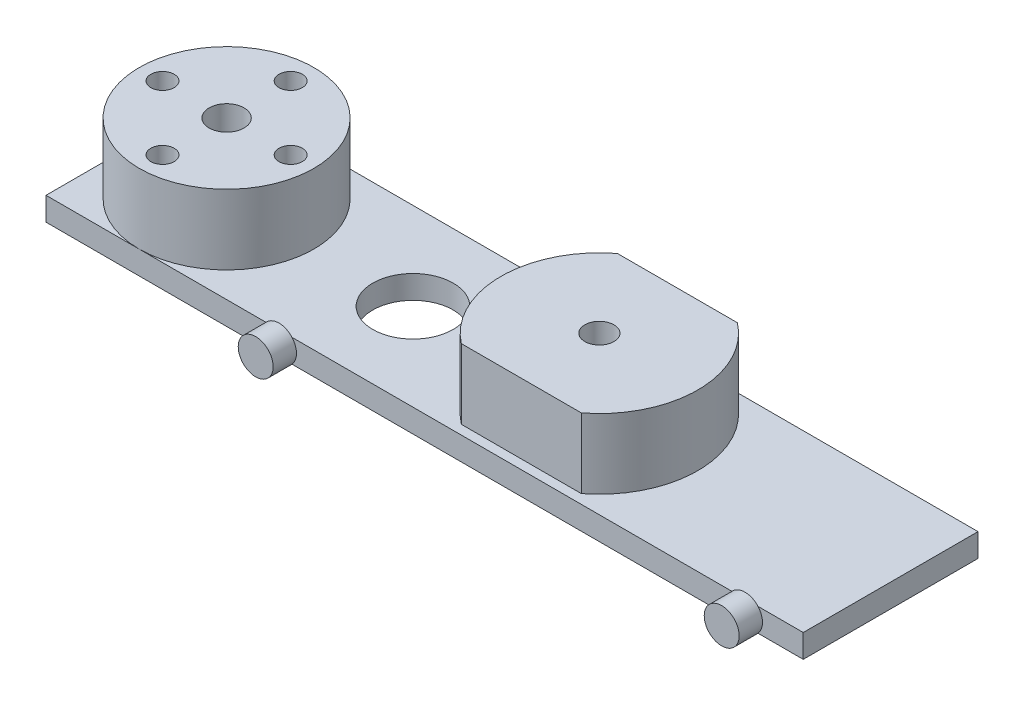
SolidWorks part; units mm, degrees
ref_plane "前视基准面" through (0, 0, 0) normal (0, 0, 1) x (1, 0, 0)
ref_plane "上视基准面" through (0, 0, 0) normal (0, 1, 0) x (1, 0, 0)
ref_plane "右视基准面" through (0, 0, 0) normal (1, 0, 0) x (0, 0, -1)
other "Configuration Table"
sketch "草图1" plane through (0, 0, 0) normal (0, 1, 0) x (1, 0, 0)
  line L0 (0, 7.5) -> (0, -7.5) construction
  line L1 (-25, 7.5) -> (25, 7.5)
  line L2 (-25, 7.5) -> (-25, -7.5)
  line L3 (-25, -7.5) -> (25, -7.5)
  line L4 (25, 7.5) -> (25, -7.5)
  line L5 (-25, 0) -> (25, 0) construction
  line L7 (-25, -7.5) -> (-40, -7.5)
  line L10 (-25, -7.5) -> (-25, 7.5)
  line L11 (-25, 7.5) -> (-40, 7.5)
  line L12 (-40, -7.5) -> (-40, 7.5)
  line L14 (-25, 7.5) -> (-40, 7.5)
  dimension "D1" = 50
  dimension "D2" = 15
  dimension "D6" = 15
  dimension "D7" = 15
extrude "凸台-拉伸1" add sketch "草图1" along normal blind 2 contours L11 L2 | L2 L1 L4 L3 | L10 L7 L12 L11 region at (-32.5, 0, 0)
sketch "草图2" plane through (0, 0, 0) normal (0, 1, 0) x (1, 0, 0)
  line L0 (0, 7.5) -> (0, -7.5) construction
  line L1 (25, 7.5) -> (-40, 7.5) construction
  line L2 (-32, 7.5) -> (-32, -7.5) construction
  line L3 (-40, -7.5) -> (-40, 7.5) construction
  line L4 (-25, 7.5) -> (-25, -7.5) construction
  line L6 (-25, -7.5) -> (25, -7.5) construction
  line L10 (-40, 0) -> (-25, 0) construction
  line L14 (-40, -7.5) -> (25, -7.5) construction
  circle A2 centre (0, 0) radius 1.25
  circle A3 centre (16, 0) radius 4.1
  circle A4 centre (16, 0) radius 3.45
  circle A5 centre (-16, 0) radius 4.1
  circle A6 centre (-16, 0) radius 3.45
  circle A8 centre (24, 0) radius 1.25
  circle A9 centre (-24, 0) radius 1.25
  circle A11 centre (-32, 0) radius 1.5
  circle A12 centre (-26.5, 0) radius 1
  circle A13 centre (-32, -5.5) radius 1
  circle A14 centre (-37.5, 0) radius 1
  circle A15 centre (-32, 5.5) radius 1
  point P36 (0, -7.5)
  dimension "D3" = 2.5
  dimension "D4" = 6.9
  dimension "D5" = 8.2
  dimension "D7" = 15
  dimension "D8" = 2.5
  dimension "D11" = 3
  dimension "D12" = 2
  dimension "D2" = 8
  dimension "D6" = 16
  dimension "D10" = 8
  dimension "D13" = 5.5
  dimension "D17" = 7.5
  dimension "D14" = 4
extrude "切除-拉伸1" cut sketch "草图2" along normal up to surface (2 mm away) contours A2 | A6 | A14 | A11 | A13 | A12 | A15 up to face at (-7.5, 2, 0)
sketch "草图4" plane through (0, 0, 7.5) normal (0, 0, 1) x (1, 0, 0)
  line L0 (25, 1) -> (-40, 1) construction
  line L1 (25, 2) -> (25, 0) construction
  line L2 (-40, 2) -> (-40, 0) construction
  line L3 (0, 0) -> (0, 2) construction
  line L5 (25, 2) -> (25, 0) construction
  line L6 (-40, 2) -> (25, 2) construction
  circle A0 centre (20, 1) radius 1.5
  circle A1 centre (-20, 1) radius 1.5
  dimension "D1" = 3
  dimension "D2" = 3
  dimension "D3" = 20
  dimension "D4" = 20
  dimension "D5" = 25
extrude "凸台-拉伸2" add sketch "草图4" along normal blind 2
sketch "草图5" plane through (0, 2, 0) normal (0, 1, 0) x (1, 0, 0)
  line L0 (0, 0) -> (0, 4.126) construction
  line L1 (4.9054, -6) -> (-4.9054, -6)
  line L2 (-4.7026, 0) -> (-2.9861, 0) construction
  line L3 (4.9054, 6) -> (-4.9054, 6)
  line L4 (5.149, -6.7) -> (-5.149, -6.7)
  line L5 (5.149, 6.7) -> (-5.149, 6.7)
  arc A0 (-4.9054, 6) -> (-4.9054, -6) centre (0, 0) ccw
  arc A1 (4.9054, -6) -> (4.9054, 6) centre (0, 0) ccw
  arc A2 (-5.149, 6.7) -> (-5.149, -6.7) centre (0, 0) ccw
  arc A3 (5.149, -6.7) -> (5.149, 6.7) centre (0, 0) ccw
  circle A4 centre (-32, 0) radius 7.5
  circle A5 centre (-32, 0) radius 7.2
  point P14 (0, -6)
  point P15 (0, 6)
  point P21 (0, -6.7)
  point P22 (0, 6.7)
  circle M9 centre (0, 0) radius 1.25
  dimension "D1" = 15.5
  dimension "D3" = 16.9
  dimension "D5" = 14.4
  dimension "D6" = 15
  dimension "D2" = 12
  dimension "D4" = 13.4
extrude "凸台-拉伸3" add sketch "草图5" along normal blind 6
extrude "凸台-拉伸4" add sketch "草图5<8>" along direction (0, 1, 0) on the side of the normal up to surface (6 mm away) contours L1 A1 L3 A0 M9 | A5 region at (0, 2, 5.804) up to face at (0, 8, 0)
sketch "草图5<8>" plane through (0, 2, 0) normal (0, 1, 0) x (1, 0, 0) same geometry as "草图5"
extrude "切除-拉伸2" cut sketch "草图5<11>" against normal through all and the other way offset from surface 2.5 contours L1 A1 L3 A0 M9 | A5 region at (0, 2, 5.804) other way up to face at (0, 8, 0)
sketch "草图5<11>" plane through (0, 2, 0) normal (0, 1, 0) x (1, 0, 0) same geometry as "草图5"
extrude "切除-拉伸3" cut sketch "草图2<3>" along normal up to surface (8 mm away) contours A11 | A15 | A14 | A13 | A12 region at (-32, 0, 0) region at (-32, 0, 5.5) region at (-37.5, 0, 0) region at (-32, 0, -5.5) up to face at (-32, 8, 7.5)
sketch "草图2<3>" plane through (0, 0, 0) normal (0, 1, 0) x (1, 0, 0) same geometry as "草图2"
